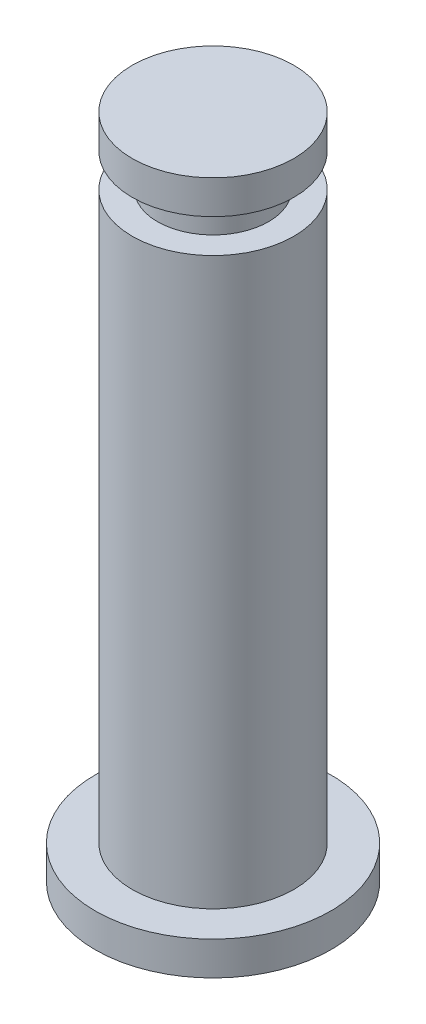
SolidWorks part; units mm, degrees
ref_plane "Alzado" through (0, 0, 0) normal (0, 0, 1) x (1, 0, 0)
ref_plane "Planta" through (0, 0, 0) normal (0, 1, 0) x (1, 0, 0)
ref_plane "Vista lateral" through (0, 0, 0) normal (1, 0, 0) x (0, 0, -1)
sketch "Croquis1" plane through (0, 0, 0) normal (0, 1, 0) x (1, 0, 0)
  circle A0 centre (0, 0) radius 3.5
  circle A1 centre (0, 0) radius 2.4
  dimension "D1" = 7
  dimension "D2" = 4.8
extrude "Saliente-Extruir1" add sketch "Croquis1" along normal blind 1
extrude "Saliente-Extruir2" add sketch "Croquis1<2>" along normal blind 19.8 contours A1 region at (0, 0, 0)
sketch "Croquis1<2>" plane through (0, 0, 0) normal (0, 1, 0) x (1, 0, 0) same geometry as "Croquis1"
sketch "Croquis2" plane through (0, 19.8, 0) normal (0, 1, 0) x (1, 0, 0)
  circle A0 centre (0, 0) radius 1.65
  circle A2 centre (0, 0) radius 2.4
  circle A3 centre (0, 0) radius 2.4
  dimension "D2" = 0.75
  dimension "D1" = 0
extrude "Cortar-Extruir1" cut sketch "Croquis2" against normal blind 1 from offset 1 offset against normal yes
